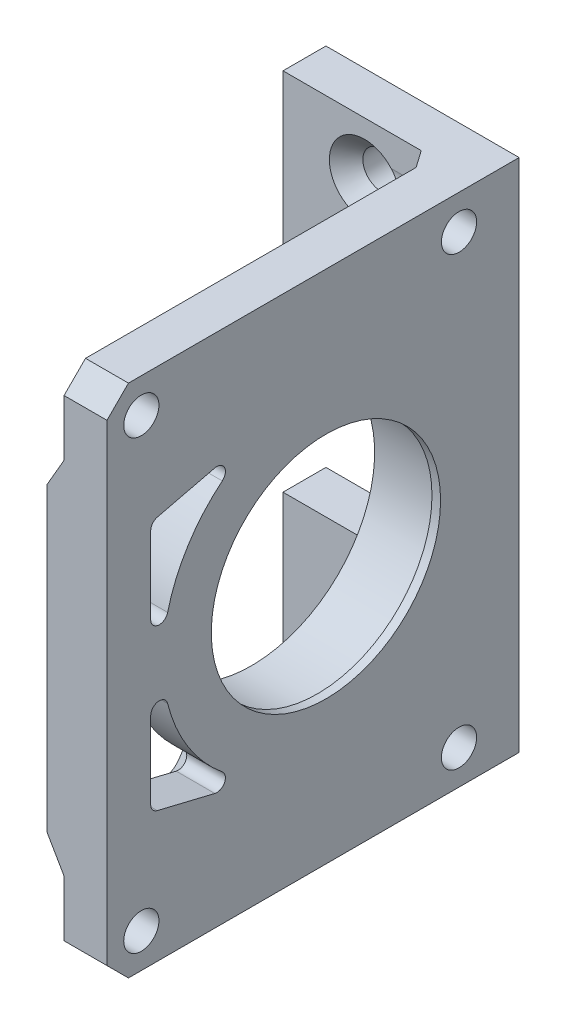
SolidWorks part; units mm, degrees
ref_plane "前视基准面" through (0, 0, 0) normal (0, 0, 1) x (1, 0, 0)
ref_plane "上视基准面" through (0, 0, 0) normal (0, 1, 0) x (1, 0, 0)
ref_plane "右视基准面" through (0, 0, 0) normal (1, 0, 0) x (0, 0, -1)
sketch "草图2" plane through (0, 0, 0) normal (0, 0, 1) x (1, 0, 0)
  line L0 (-14.7736, 24.3382) -> (-14.7736, -35.6618)
  line L1 (-14.7736, -35.6618) -> (30.2264, -35.6618)
  line L2 (7.7264, -35.6618) -> (7.7264, -18.1618)
  line L3 (21.55, -18.1618) -> (-6.0971, -18.1618)
  line L4 (-6.0971, -18.1618) -> (-6.0971, 6.8382)
  line L5 (-6.0971, 6.8382) -> (21.55, 6.8382)
  line L6 (7.7264, 6.8382) -> (7.7264, 24.3382)
  line L7 (30.2264, 24.3382) -> (-14.7736, 24.3382)
  line L8 (7.7264, 28.8603) -> (7.7264, -39.8897) construction
  line L9 (21.55, -18.1618) -> (21.55, 6.8382)
  line L10 (30.2264, 24.3382) -> (30.2264, -35.6618)
  line L11 (-18.1559, -5.6618) -> (33.2411, -5.6618) construction
  point P16 (-6.0971, -5.6618)
  point P17 (-14.7736, -5.6618)
  dimension "D1" = 45
  dimension "D2" = 25
  dimension "D3" = 60
extrude "凸台-拉伸2" add sketch "草图2" along normal blind 5 contours L6 L7 L0 L1 L2 L3 L4 L5 | L10 L7 L6 L5 L9 L3 L2 L1 region at (-3.5236, 23.6974, 0) region at (18.9764, 23.6974, 0)
sketch "草图4" plane through (0, 0, 5) normal (0, 0, 1) x (1, 0, 0)
  line L0 (-18.165, -5.6618) -> (33.9165, -5.6618) construction
  line L1 (-14.7736, 24.3382) -> (-14.7736, -35.6618) construction
  line L2 (-14.7736, -23.1618) -> (-6.0971, -23.1618)
  line L3 (-14.7736, -23.1618) -> (-14.7736, 11.8382)
  line L4 (-14.7736, 11.8382) -> (-6.0971, 11.8382)
  line L5 (-6.0971, -23.1618) -> (-6.0971, 11.8382)
  line L6 (-6.0971, -18.1618) -> (-6.0971, 6.8382) construction
  line L7 (7.7264, -39.813) -> (7.7264, 28.1228) construction
  line L8 (30.2264, 11.8382) -> (21.55, 11.8382)
  line L9 (21.55, -23.1618) -> (21.55, 11.8382)
  line L10 (30.2264, -23.1618) -> (21.55, -23.1618)
  line L11 (30.2264, -23.1618) -> (30.2264, 11.8382)
  point P17 (-14.7736, -5.6618)
  dimension "D1" = 35
extrude "凸台-拉伸15" add sketch "草图4" along normal blind 35
sketch "草图5" plane through (-14.7736, 0, 0) normal (-1, 0, 0) x (0, 0, 1)
  line L0 (0, -5.6618) -> (40, -5.6618)
  line L1 (0, 24.3382) -> (0, -35.6618) construction
  line L2 (40, 11.8382) -> (40, -23.1618) construction
  line L3 (22.5, 11.8382) -> (40, 11.8382)
  line L4 (40, 11.8382) -> (40, -23.1618)
  line L5 (40, -23.1618) -> (22.5, -23.1618)
  circle A0 centre (22.5, -5.6618) radius 17.5
  line M5 (5, -23.1618) -> (40, -23.1618)
  line M6 (40, -23.1618) -> (40, 11.8382)
  line M7 (40, 11.8382) -> (5, 11.8382)
  dimension "D1" = 35
extrude "切除-拉伸1" cut sketch "草图5" against normal blind 45 contours A0 M5 M6 | A0 M6 M7 region at (-14.7736, 7.9293, 36.0911) region at (-14.7736, -19.2528, 36.0911)
sketch "草图6" plane through (-14.7736, 0, 0) normal (-1, 0, 0) x (0, 0, 1)
  circle A0 centre (22.5, -5.6618) radius 14.35
  dimension "D1" = 28.7
extrude "切除-拉伸2" cut sketch "草图6" against normal blind 45
fillet "圆角1" radius 5 4 edges at (-6.0971, 6.8382, 2.5) (21.55, 6.8382, 2.5) (-6.0971, -18.1618, 2.5) (21.55, -18.1618, 2.5)
sketch "草图7" plane through (-6.0971, 0, 0) normal (1, 0, 0) x (0, 0, -1)
  circle A0 centre (-22.5, -5.6618) radius 15
  circle A1 centre (-22.5, -5.6618) radius 13
extrude "凸台-拉伸16" add sketch "草图7" against normal blind 1
sketch "草图8" plane through (21.55, 0, 0) normal (-1, 0, 0) x (0, 0, 1)
  circle A0 centre (22.5, -5.6618) radius 15
  circle A1 centre (22.5, -5.6618) radius 10
sketch "草图9" plane through (0, 0, 5) normal (0, 0, 1) x (1, 0, 0)
  line L0 (7.7264, 24.3382) -> (7.7264, -35.6618)
  line L13 (30.2264, 24.3382) -> (-14.7736, 24.3382) construction
  line L14 (-14.7736, -35.6618) -> (30.2264, -35.6618) construction
sketch "草图11" plane through (0, 0, 5) normal (0, 0, 1) x (1, 0, 0)
  line L0 (-14.7736, 18.0882) -> (30.2264, 18.0882)
  line L1 (-14.7736, 24.3382) -> (-14.7736, 11.8382) construction
  line L2 (30.2264, 24.3382) -> (30.2264, 11.8382) construction
  line L3 (7.7264, 24.3382) -> (7.7264, -35.6618) construction
  line L4 (30.2264, 24.3382) -> (-14.7736, 24.3382) construction
  line L5 (-14.7736, -35.6618) -> (30.2264, -35.6618) construction
  line L6 (7.7264, -5.6618) -> (45.6912, -5.6618) construction
  line L7 (45.6912, -5.6618) -> (45.6912, 4.9969) construction
  line L10 (-14.7736, -29.4118) -> (30.2264, -29.4118)
  line L11 (-14.7736, -23.1618) -> (-14.7736, -35.6618) construction
  point P4 (-1.7736, 18.0882)
  point P16 (-1.7736, -29.4118)
  point P18 (17.2264, -29.4118)
  point P25 (17.2264, 18.0882)
  dimension "D1" = 13
split "分割1" trim tools "草图9" bodies to split 111 resulting bodies 117 118
delete or keep bodies "实体-删除/保留 2" type delete bodies bodies 117
hole_wizard "打孔尺寸(%根据)内六角花形半沉头螺钉的类型1" positions "3D草图2" profile "草图31" countersink size "M6" standard "GB"
sketch3d "3D草图2"
  point P0 (17.2264, 18.0882, 5)
  point P3 (17.2264, -29.4118, 5)
sketch "草图31" plane through (17.2264, 18.0882, 5) normal (1, 0, 0) x (0, -1, 0)
  line L0 (0, 0) -> (0, 6.2919)
  line L1 (0, 6.2919) -> (2.15, 5)
  line L2 (2.15, 5) -> (2.15, 1.95)
  line L3 (2.15, 1.95) -> (4.1, 0)
  line L5 (4.1, 0) -> (0, 0)
  line L6 (-2.15, 1.95) -> (-4.1, 0) construction
  line L10 (0, 6.2919) -> (-2.15, 5) construction
  line L11 (0, -6.35) -> (0, 107.95) construction
  dimension "孔直径" = 4.3
  dimension "孔深度" = 5
  dimension "近端锥形沉头孔直径" = 8.2
  dimension "近端锥形沉头孔角度" = 90
  dimension "导头角度" = 118
sketch "草图17" [suppressed] plane through (0, 0, 5) normal (0, 0, 1) x (1, 0, 0)
  line L5 (30.2264, 31.8382) -> (27.2264, 31.8382)
  line L6 (30.2264, 31.8382) -> (30.2264, 18.8382)
  line L7 (30.2264, 18.8382) -> (27.2264, 18.8382)
  line L8 (27.2264, 31.8382) -> (27.2264, 18.8382)
  line L9 (30.2264, 24.3382) -> (30.2264, 11.8382) construction
  line L10 (30.2264, 11.8382) -> (21.55, 11.8382) construction
  dimension "D1" = 3
  dimension "D4" = 13
  dimension "D6" = 7
extrude "凸台-拉伸20" [suppressed] add sketch "草图17" along normal blind 42
sketch "草图18" [suppressed] plane through (30.2264, 0, 0) normal (1, 0, 0) x (0, 0, -1)
  line L3 (-47, 18.8382) -> (-47, 31.8382)
  arc A0 (-47, 31.8382) -> (-47, 18.8382) centre (-47, 25.3382) ccw
extrude "凸台-拉伸21" [suppressed] add sketch "草图18" against normal blind 3
sketch "草图19" [suppressed] plane through (30.2264, 0, 0) normal (1, 0, 0) x (0, 0, -1)
  circle A0 centre (-47, 25.3382) radius 1.6
  circle A2 centre (-10, 25.3382) radius 1.6
  dimension "D1" = 37
extrude "切除-拉伸3" [suppressed] cut sketch "草图19" against normal blind 3
sketch "草图24" [suppressed] plane through (30.2264, 0, 0) normal (1, 0, 0) x (0, 0, -1)
  line L11 (-5, 18.8382) -> (-38, 18.8382)
  line L12 (-5, 18.8382) -> (-5, 11.8382)
  line L14 (-38, 18.8382) -> (-38, 2.4623) construction
  line L15 (-22.5, 11.8382) -> (-5, 11.8382) construction
  line L16 (-22.5, 11.8382) -> (-5, 11.8382)
  line L19 (-5, 11.8382) -> (-5, -23.1618) construction
  line L21 (-38, 2.4623) -> (-38, -13.7858) construction
  arc A2 (-22.5, 11.8382) -> (-22.5, -23.1618) centre (-22.5, -5.6618) ccw construction
  arc A3 (-22.5, 11.8382) -> (-38, 2.4623) centre (-22.5, -5.6618) ccw
  arc A4 (-38, 2.4623) -> (-38, -13.7858) centre (-22.5, -5.6618) ccw construction
  arc A6 (-38, 2.4623) -> (-38, 18.8382) centre (-53.622, 10.6503) ccw
  dimension "D1" = 33
extrude "凸台-拉伸25" [suppressed] add sketch "草图24" against normal blind 3
sketch "草图21" [suppressed] plane through (0, 0, 5) normal (0, 0, 1) x (1, 0, 0)
  line L1 (30.2264, 18.8382) -> (30.2264, 31.8382) construction
  line L5 (18.2264, 24.3382) -> (30.2264, 24.3382)
  line L6 (27.2264, 24.3382) -> (7.7264, 24.3382) construction
  line L8 (30.2264, 24.3382) -> (30.2264, 31.8382)
  line L9 (26.4082, 31.8382) -> (18.2264, 24.3382)
  line L15 (30.2264, 31.8382) -> (26.4082, 31.8382)
  line L16 (30.2264, 31.8382) -> (30.2264, 35.3382) construction
  line L17 (30.2264, 35.3382) -> (26.4082, 31.8382) construction
  dimension "D3" = 12
  dimension "D4" = 11
extrude "凸台-拉伸22" [suppressed] add sketch "草图21" against normal blind 5
sketch "草图34" [suppressed] plane through (0, 0, 5) normal (0, 0, 1) x (1, 0, 0)
  line L0 (30.2264, -23.1618) -> (30.2264, -35.6618) construction
  line L1 (21.0721, -35.192) -> (23.3702, -37.1203)
  line L2 (21.0721, -35.192) -> (29.4283, -25.2334)
  line L3 (29.4283, -25.2334) -> (30.2264, -25.9031)
  line L4 (23.3702, -37.1203) -> (30.2264, -28.9494)
  line L5 (21.0721, -35.192) -> (31.7264, -27.1618) construction
  line L6 (29.4283, -25.2334) -> (23.3702, -37.1203) construction
  line L7 (21.55, -23.1618) -> (30.2264, -23.1618) construction
  line L8 (30.2264, -25.9031) -> (30.2264, -28.9494)
  line L9 (30.2264, -28.9494) -> (31.7264, -27.1618) construction
  line L10 (30.2264, -25.9031) -> (31.7264, -27.1618) construction
  point P0 (26.3992, -31.1769)
  dimension "D1" = 3
  dimension "D2" = 13
  dimension "D3" = 40
  dimension "D4" = 4
  dimension "D5" = 1.5
extrude "凸台-拉伸26" [suppressed] add sketch "草图34" along normal blind 42
sketch "草图37" [suppressed] plane through (30.2264, 0, 0) normal (1, 0, 0) x (0, 0, -1)
  line L0 (-40, -5.6618) -> (-5, -5.6618) construction
  line L1 (-5, 24.3382) -> (-5, -35.6618) construction
  line L3 (-37.4223, -28.9494) -> (-5, -28.9494)
  line L4 (-5, -28.9494) -> (-5, -23.1618)
  line L5 (-22.5, -23.1618) -> (-5, -23.1618) construction
  line L6 (-22.5, -23.1618) -> (-5, -23.1618)
  arc A0 (-38, 2.4623) -> (-22.5, -23.1618) centre (-22.5, -5.6618) ccw construction
  arc A1 (-38, 2.4623) -> (-38, 18.8382) centre (-53.622, 10.6503) ccw construction
  arc A2 (-38, 2.4623) -> (-38, 18.8382) centre (-53.622, 10.6503) ccw construction
  arc A3 (-38, -13.7858) -> (-37.4223, -28.9494) centre (-53.622, -21.9738) cw
  arc A5 (-38, -13.7858) -> (-22.5, -23.1618) centre (-22.5, -5.6618) ccw
extrude "凸台-拉伸27" [suppressed] add sketch "草图37" against normal blind 2.6
sketch "草图38" [suppressed] plane through (0, 0, 5) normal (0, 0, 1) x (1, 0, 0)
  line L3 (30.2264, -35.6618) -> (30.2264, -28.9494)
  line L4 (30.2264, -28.9494) -> (24.5941, -35.6618)
  line L5 (24.5941, -35.6618) -> (30.2264, -35.6618)
  line L6 (30.2264, -35.6618) -> (30.2264, -28.9494)
  line L7 (30.2264, -28.9494) -> (24.5941, -35.6618)
  line L8 (24.5941, -35.6618) -> (30.2264, -35.6618)
  dimension "D1" = 0
extrude "切除-拉伸5" [suppressed] cut sketch "草图38" against normal blind 22.6
sketch "草图39" [suppressed] plane through (0, 0, 5) normal (0, 0, 1) x (1, 0, 0)
  line L4 (24.5941, -35.6618) -> (21.6319, -35.6618)
  line L5 (23.3702, -37.1203) -> (24.5941, -35.6618)
  line L6 (21.6319, -35.6618) -> (23.3702, -37.1203)
  line L8 (24.5941, -35.6618) -> (21.6319, -35.6618)
  line L9 (23.3702, -37.1203) -> (24.5941, -35.6618)
  line L10 (21.6319, -35.6618) -> (23.3702, -37.1203)
  dimension "D1" = 0
sketch "草图41" [suppressed] plane through (31.9924, -26.8448, 0) normal (0.766, -0.6428, 0) x (0, 0, -1)
  line L1 (-47, -13.4138) -> (-47, -0.4138)
  line L2 (-47, -13.4138) -> (-47, -2.7474) construction
  line L3 (-47, -13.4138) -> (-5, -13.4138) construction
  arc A0 (-47, -0.4138) -> (-47, -13.4138) centre (-47, -6.9138) ccw
  line M5 (-47, -2.7474) -> (-47, -13.4138)
extrude "凸台-拉伸29" [suppressed] add sketch "草图41" against normal up to surface (3 mm away) contours A0 M5
sketch "草图42" [suppressed] plane through (31.9924, -26.8448, 0) normal (0.766, -0.6428, 0) x (0, 0, -1)
  line L0 (-47, -6.9138) -> (-10, -6.9138) construction
  circle A0 centre (-47, -6.9138) radius 1.5
  circle A1 centre (-10, -6.9138) radius 1.5
  dimension "D1" = 3
  dimension "D2" = 37
extrude "切除-拉伸6" [suppressed] cut sketch "草图42" against normal through all
sketch "草图44" [suppressed] plane through (0, 0, 47) normal (0, 0, -1) x (-1, 0, 0)
  line L3 (-31.7264, -27.1618) -> (-30.2264, -28.9494)
  line L4 (-30.2264, -28.9494) -> (-30.2264, -25.9031)
  line L5 (-30.2264, -25.9031) -> (-31.7264, -27.1618)
  line L6 (-31.7264, -27.1618) -> (-30.2264, -28.9494)
  line L7 (-30.2264, -28.9494) -> (-30.2264, -25.9031)
  line L8 (-30.2264, -25.9031) -> (-31.7264, -27.1618)
  dimension "D1" = 0
extrude "切除-拉伸7" [suppressed] cut sketch "草图44" against normal blind 8.6
extrude "凸台-拉伸31" [suppressed] add sketch "草图39" against normal up to surface (5 mm away) up to face at (19.3764, 18.0882, 0)
sketch "草图45" plane through (0, 0, 5) normal (0, 0, 1) x (1, 0, 0)
  line L0 (30.2264, -23.1618) -> (21.8702, -33.1203)
  line L1 (30.2264, -23.1618) -> (30.2264, -35.6618) construction
  line L2 (26.0483, -28.1411) -> (20.7952, -23.7332) construction
  line L4 (23.2264, 11.8382) -> (23.2264, 24.3382)
  line L5 (30.2264, 11.8382) -> (21.55, 11.8382) construction
  line L6 (30.2264, 24.3382) -> (7.7264, 24.3382) construction
  line L7 (30.2264, 24.3382) -> (30.2264, 11.8382) construction
  line L8 (23.2264, 18.0882) -> (32.7405, 18.0882) construction
  dimension "D1" = 40
  dimension "D2" = 7
  dimension "D3" = 13
sketch "草图47" plane through (0, 0, 5) normal (0, 0, 1) x (1, 0, 0)
  line L7 (30.2264, 24.3382) -> (7.7264, 24.3382) construction
  line L8 (25.2264, 24.3382) -> (30.2264, 24.3382)
  line L9 (25.2264, 24.3382) -> (25.2264, 15.3023)
  line L10 (25.2264, 11.8382) -> (30.2264, 11.8382)
  line L11 (30.2264, 24.3382) -> (30.2264, 11.8382)
  line L12 (30.2264, 11.8382) -> (21.55, 11.8382) construction
  line L13 (23.2264, 11.8382) -> (23.2264, 24.3382) construction
  line L14 (23.2264, 11.8382) -> (25.2264, 15.3023)
  line L15 (23.2264, 11.8382) -> (25.2264, 11.8382)
  line L16 (25.2264, 15.3023) -> (25.2264, 11.8382) construction
  dimension "D1" = 5
  dimension "D2" = 2
  dimension "D3" = 30
extrude "凸台-拉伸35" add sketch "草图47" along normal blind 43
sketch "草图46" plane through (0, 0, 5) normal (0, 0, 1) x (1, 0, 0)
  line L9 (7.7264, -5.6618) -> (45.6912, -5.6618) construction
  line L16 (7.7264, -5.6618) -> (45.6912, -5.6618) construction
  line L17 (30.2264, -35.6618) -> (25.2264, -35.6618)
  line L18 (30.2264, -23.1618) -> (30.2264, -35.6618)
  line L19 (23.2264, -23.1618) -> (30.2264, -23.1618)
  line L20 (25.2264, 24.3382) -> (25.2264, 15.3023)
  line L21 (25.2264, 15.3023) -> (23.2264, 11.8382)
  line L22 (23.2264, 11.8382) -> (30.2264, 11.8382)
  line L23 (30.2264, 11.8382) -> (30.2264, 24.3382)
  line L24 (30.2264, 24.3382) -> (25.2264, 24.3382)
  line L25 (25.2264, 24.3382) -> (25.2264, 15.3023) construction
  line L26 (25.2264, 15.3023) -> (23.2264, 11.8382) construction
  line L27 (23.2264, 11.8382) -> (30.2264, 11.8382) construction
  line L28 (30.2264, 11.8382) -> (30.2264, 24.3382) construction
  line L29 (30.2264, 24.3382) -> (25.2264, 24.3382) construction
  line L30 (25.2264, -26.6259) -> (23.2264, -23.1618)
  line L31 (25.2264, -35.6618) -> (25.2264, -26.6259)
  dimension "D1" = 0
extrude "凸台-拉伸34" add sketch "草图46" along normal blind 43
sketch "草图50" plane through (0, 0, 5) normal (0, 0, 1) x (1, 0, 0)
  line L0 (23.2264, -31.504) -> (23.2264, 11.8382)
  line L1 (30.2264, -23.1618) -> (21.8702, -33.1203) construction
sketch "草图51" plane through (0, 0, 5) normal (0, 0, 1) x (1, 0, 0)
  line L3 (25.2264, -35.6618) -> (25.2264, -26.6259)
  line L5 (7.7264, -35.6618) -> (25.2264, -35.6618)
  line L8 (7.7264, -35.6618) -> (25.2264, -35.6618)
  line L12 (23.2264, -23.1618) -> (21.55, -23.1618)
  line L13 (23.2264, -23.1618) -> (21.55, -23.1618)
  line L14 (21.55, -23.1618) -> (21.55, -13.1618)
  line L15 (21.55, -23.1618) -> (21.55, -13.1618)
  line L16 (16.55, -18.1618) -> (7.7264, -18.1618)
  line L17 (16.55, -18.1618) -> (7.7264, -18.1618)
  line L18 (7.7264, -18.1618) -> (7.7264, -35.6618)
  line L19 (7.7264, -18.1618) -> (7.7264, -35.6618)
  line L21 (25.2264, -35.6618) -> (25.2264, -26.6259)
  line L22 (25.2264, -26.6259) -> (23.2264, -23.1618)
  line L23 (25.2264, -26.6259) -> (23.2264, -23.1618)
  arc A1 (16.55, -18.1618) -> (21.55, -13.1618) centre (16.55, -13.1618) ccw
  arc A2 (16.55, -18.1618) -> (21.55, -13.1618) centre (16.55, -13.1618) ccw
  dimension "D1" = 0
sketch "草图53" plane through (30.2264, 0, 0) normal (1, 0, 0) x (0, 0, -1)
  line L0 (-22.5, 8.6882) -> (-22.5, -20.0118) construction
  line L1 (-48, 11.8382) -> (-22.5, 11.8382)
  line L2 (-48, 11.8382) -> (-48, -23.1618)
  line L3 (-48, -23.1618) -> (-22.5, -23.1618)
  line L4 (-22.5, 11.8382) -> (-22.5, 8.6882)
  line L5 (-22.5, -20.0118) -> (-22.5, -23.1618)
  circle A0 centre (-22.5, -5.6618) radius 14.35 construction
  arc A1 (-22.5, 8.6882) -> (-22.5, -20.0118) centre (-22.5, -5.6618) ccw
  arc A2 (-22.5, -20.0118) -> (-22.5, 8.6882) centre (-22.5, -5.6618) ccw construction
extrude "凸台-拉伸36" add sketch "草图53" against normal blind 7
sketch "草图54" plane through (30.2264, -32.4654, 0) normal (-1, 0, 0) x (0, 0, -1)
  line L0 (-48, -0.8037) -> (0, -0.8037) construction
  line L3 (0, -5.8396) -> (0, -9.3037) construction
  line L6 (-48, -9.3037) -> (-48, -5.8396) construction
  line L7 (-48, 3.1963) -> (-48, -56.8037) construction
  line L8 (-48, 3.1963) -> (-5, 3.1963) construction
  line L9 (-48, -5.8396) -> (-48, 3.1963) construction
  circle A0 centre (-44, -0.8037) radius 2.05
  circle A1 centre (-7, -0.8037) radius 2.05
  dimension "D1" = 4.1
  dimension "D2" = 37
  dimension "D4" = 4
  dimension "D3" = 4
extrude "切除-拉伸10" cut sketch "草图54" along normal blind 14
sketch "草图55" plane through (30.2264, 0, 0) normal (1, 0, 0) x (0, 0, -1)
  line L0 (-48, 24.3382) -> (-48, 16.3382) construction
  line L1 (-48, 24.3382) -> (0, 24.3382) construction
  line L2 (-48, 20.3382) -> (0, 20.3382) construction
  line L3 (0, 24.3382) -> (0, -35.6618) construction
  line L4 (-25.5, 17.8382) -> (-25.5, 24.3382) construction
  line L6 (-48, -35.6618) -> (-48, 24.3382) construction
  circle A0 centre (-44, 20.3382) radius 2.05
  circle A1 centre (-7, 20.3382) radius 2.05
  dimension "D2" = 4.1
  dimension "D3" = 37
  dimension "D1" = 4
  dimension "D4" = 4
extrude "切除-拉伸11" cut sketch "草图55" against normal blind 14
sketch "草图58" plane through (30.2264, 0, 0) normal (1, 0, 0) x (0, 0, -1)
  circle A0 centre (-22.5, -5.6618) radius 14.35 construction
  circle A1 centre (-22.5, -5.6618) radius 14.35
extrude "拉伸-薄壁1" add sketch "草图58" against normal blind 1 thin thin type one direction reverse wall 1
chamfer "倒角2" distance 1.4 angle 55 10 edges at (22.3882, 11.8382, 5) (24.2264, 13.5703, 5) (25.2264, 22.5632, 5) (25.2264, 17.5953, 5) (22.3882, -23.1618, 5) (21.55, -18.1618, 5) (25.2264, -33.8868, 5) (25.2264, -28.9188, 5) (24.2264, -24.8938, 5) (21.55, 6.8382, 5) first distance on face at (19.5578, 15.0866, 5) first distance on face at (19.5578, -26.4101, 5)
chamfer "Chamfer1" distance 2.5 angle 45 2 edges at (27.7264, 24.3382, 48) (27.7264, -35.6618, 48)
sketch "Sketch2" plane through (30.2264, 0, 0) normal (1, 0, 0) x (0, 0, -1)
  line L0 (-35.4425, 10.7544) -> (-42.1423, 9.133)
  line L1 (-42.907, 8.161) -> (-42.907, -0.8279)
  line L2 (-22.5, -5.6618) -> (-28.2636, -5.6618) construction
  line L3 (-42.907, -19.4846) -> (-42.907, -10.4957)
  line L4 (-35.4425, -22.078) -> (-42.1423, -20.4565)
  arc A0 (-34.5719, 9.0103) -> (-40.9367, -1.0695) centre (-22.5, -5.6618) ccw
  arc A1 (-42.1423, 9.133) -> (-42.907, 8.161) centre (-41.907, 8.161) ccw
  arc A2 (-35.4425, 10.7544) -> (-34.5719, 9.0103) centre (-35.2073, 9.7825) cw
  arc A3 (-42.907, -0.8279) -> (-40.9367, -1.0695) centre (-41.907, -0.8279) ccw
  arc A4 (-42.907, -10.4957) -> (-40.9367, -10.254) centre (-41.907, -10.4957) cw
  arc A5 (-35.4425, -22.078) -> (-34.5719, -20.3338) centre (-35.2073, -21.106) ccw
  arc A6 (-42.1423, -20.4565) -> (-42.907, -19.4846) centre (-41.907, -19.4846) cw
  arc A7 (-34.5719, -20.3338) -> (-40.9367, -10.254) centre (-22.5, -5.6618) cw
  point P21 (-44.1051, -8.7337)
  point P22 (-33.7797, -21.6834)
  point P23 (-40.9914, -21.862)
  point P24 (-34.0367, -19.3)
  dimension "D1" = 1
  dimension "D2" = 19
extrude "Cut-Extrude1" cut sketch "Sketch2" against normal blind 10
chamfer "Chamfer2" distance 2.5 angle 45 12 edges at (23.2264, -21.2672, 38.7924) (23.2264, -21.5526, 34.3125) (23.2264, -20.1029, 42.6929) (23.2264, -15.806, 38.5653) (23.2264, -14.9901, 42.907) (23.2264, -9.5031, 42.0288) (23.2264, -1.8204, 42.0288) (23.2264, 4.4825, 38.5653) (23.2264, 3.6666, 42.907) (23.2264, 10.2291, 34.3125) (23.2264, 8.7794, 42.6929) (23.2264, 9.9437, 38.7924)
move or copy body "实体-移动/复制3" [suppressed] bodies to move or copy 170
move or copy body "实体-移动/复制2" [suppressed] bodies to move or copy 155
move or copy body "实体-移动/复制1" [suppressed] bodies to move or copy 146
